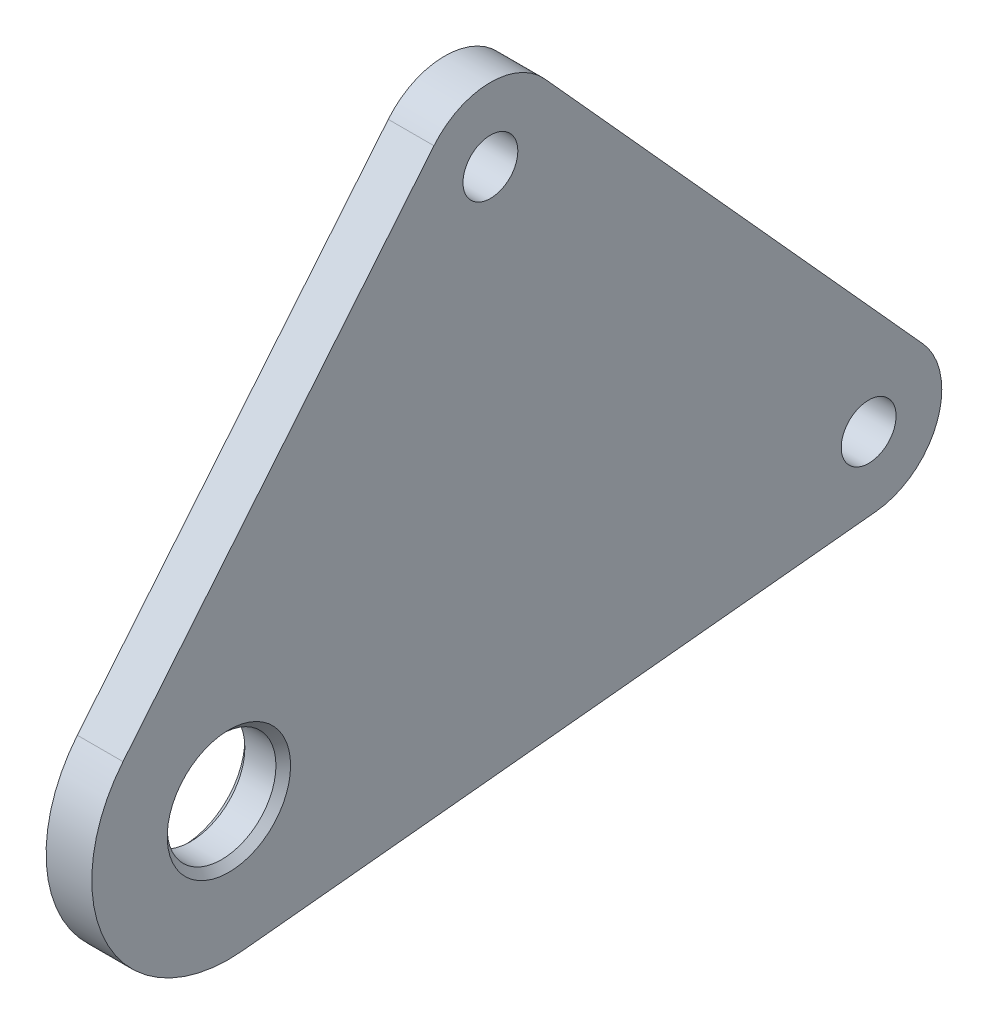
SolidWorks part; units mm, degrees
ref_plane "Front Plane" through (0, 0, 0) normal (0, 0, 1) x (1, 0, 0)
ref_plane "Top Plane" through (0, 0, 0) normal (0, 1, 0) x (1, 0, 0)
ref_plane "Right Plane" through (0, 0, 0) normal (1, 0, 0) x (0, 0, -1)
sketch "Sketch1" plane through (0, 0, 0) normal (1, 0, 0) x (0, 0, -1)
  line L0 (11.219, 25.4388) -> (-5.7915, 4.7654)
  line L1 (17.2755, 25.5792) -> (37.9677, 2.6819)
  line L2 (35.4, -3.9799) -> (0.75, -7.4624)
  line L3 (14.3078, 22.8973) -> (0, 0) construction
  line L4 (0, 0) -> (0, 22.8973) construction
  line L5 (0, 22.8973) -> (14.3078, 22.8973) construction
  circle A1 centre (14.3078, 22.8973) radius 1.5
  circle A2 centre (35, 0) radius 1.5
  circle A3 centre (0, 0) radius 2.975
  circle A4 centre (35, 0) radius 4
  circle A5 centre (14.3078, 22.8973) radius 4
  circle A6 centre (0, 0) radius 7.5
  circle A7 centre (14.3078, 22.8973) radius 3.125
  circle A8 centre (35, 0) radius 3.125
  dimension "D1" = 3
  dimension "D3" = 5.95
  dimension "D6" = 8
  dimension "D7" = 8
  dimension "D8" = 15
  dimension "D9" = 6.25
  dimension "D4" = 27
  dimension "D5" = 35
  dimension "D10" = 32
extrude "Boss-Extrude1" add sketch "Sketch1" along normal blind 2.5 contours A6 A3 | A6 L2 A4 L1 A5 L0 | A5 A1 | A4 A2 | A7 A1 | A8 A2 region at (0, 7.1261, -16.884) region at (0, 26.7831, -14.2177) region at (0, 6.8603, -2.4596) region at (0, 1.3962, -38.6274) region at (0, 22.8973, -11.2712) region at (0, 0, -31.9634)
chamfer "Chamfer1" distance 0.4 angle 45 2 edges at (2.5, 0, -2.975) (0, 0, -2.975)
